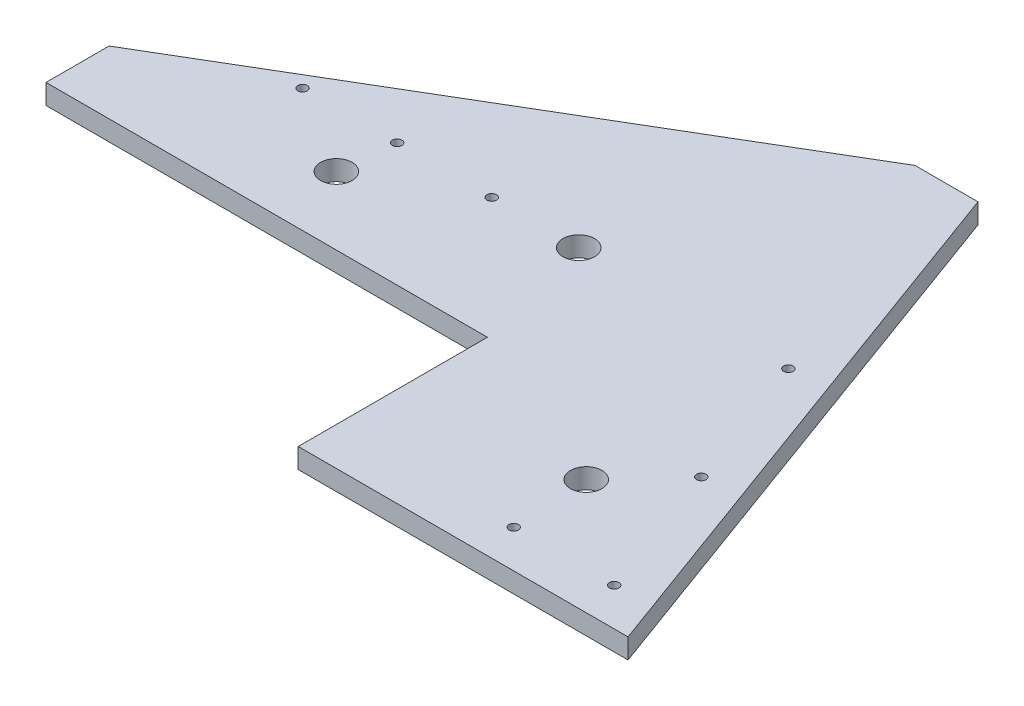
SolidWorks part; units mm, degrees
ref_plane "Front" through (0, 0, 0) normal (0, 0, 1) x (1, 0, 0)
ref_plane "Top" through (0, 0, 0) normal (0, 1, 0) x (1, 0, 0)
ref_plane "Right" through (0, 0, 0) normal (1, 0, 0) x (0, 0, -1)
sketch "Sketch1" plane through (0, 0, 0) normal (0, 1, 0) x (1, 0, 0)
  line L0 (145, 175) -> (180.6, 175)
  line L1 (0, 0) -> (145, 0)
  line L2 (0, 0) -> (0, 175)
  line L3 (0, 175) -> (145, 175)
  line L4 (145, 0) -> (145, 175)
  line L5 (180.6, 175) -> (180.6, 0)
  line L6 (180.6, 0) -> (145, 0)
  line L7 (145, 0) -> (145, 60)
  line L8 (145, 60) -> (140, 60)
  line L9 (140, 60) -> (140, 0)
  line L10 (140, 60) -> (0, 60)
  line L11 (180.6, 175) -> (160.6, 175)
  line L12 (0, 60) -> (0, 80)
  line L13 (160.6, 175) -> (0, 80)
  line L14 (0, 60) -> (70.5, 60)
  line L15 (70.5, 60) -> (70.5, 81.59)
  line L16 (70.5, 81.59) -> (129.875, 81.59)
  line L17 (180.6, 0) -> (244.6, 0)
  line L18 (244.6, 0) -> (180.6, 175)
  line L19 (129.875, 81.59) -> (129.875, 99.09)
  line L20 (244.6, 0) -> (194.75, 0)
  line L21 (194.75, 0) -> (194.75, 36.59)
  circle A0 centre (70.5, 81.59) radius 5
  circle A2 centre (129.875, 99.09) radius 5
  circle A3 centre (194.75, 36.59) radius 5
  dimension "D10" = 59.375
  dimension "D11" = 64
  dimension "D13" = 36.59
  dimension "D1" = 175
  dimension "D2" = 145
  dimension "D3" = 35.6
  dimension "D4" = 60
  dimension "D5" = 5
  dimension "D6" = 20
  dimension "D7" = 20
  dimension "D8" = 70.5
  dimension "D9" = 21.59
  dimension "D12" = 17.5
  dimension "D14" = 49.85
extrude "Boss-Extrude2" add sketch "Sketch1" along normal blind 6.35 contours A2 A0 L10 L8 L4 L13 L2 | L0 L13 L4 L6 L5 | L17 L18 L5 | L8 L9 L1 L4 region at (162.9473, 0, -86.5132) region at (88.7844, 0, -96.4223) region at (202.0355, 0, -58.6426) region at (142.5, 0, -30)
sketch "Sketch3" plane through (0, 6.35, 0) normal (0, 1, 0) x (1, 0, 0)
  line L0 (0, 60) -> (0, 99.0944)
  line L1 (0, 99.0944) -> (42.2796, 99.0944)
  line L2 (42.2796, 99.0944) -> (32.2796, 99.0944)
  line L3 (160.6, 175) -> (0, 80) construction
  line L4 (42.2796, 99.0944) -> (72.2796, 99.0944)
  line L5 (72.2796, 99.0944) -> (102.2796, 99.0944)
  line L6 (102.2796, 99.0944) -> (208.3598, 99.0944)
  line L7 (244.6, 0) -> (180.6, 175) construction
  line L8 (208.3598, 99.0944) -> (196.3598, 99.0944)
  line L9 (244.6, 0) -> (232.0087, 0)
  line L10 (244.6, 0) -> (140, 0) construction
  line L11 (240.2114, 12) -> (228.2114, 12)
  line L12 (228.2114, 12) -> (232.0087, 12)
  line L13 (232.0087, 12) -> (232.0087, 0)
  line L14 (196.3598, 99.0944) -> (228.2114, 12)
  line L15 (228.2114, 12) -> (212.2856, 55.5472)
  line L16 (212.2856, 55.5472) -> (196.3598, 99.0944)
  line L17 (228.2114, 12) -> (196.3598, 12)
  circle A0 centre (42.2796, 99.0944) radius 1.5
  circle A1 centre (72.2796, 99.0944) radius 1.5
  circle A2 centre (102.2796, 99.0944) radius 1.5
  circle A3 centre (196.3598, 99.0944) radius 1.5
  circle A4 centre (212.2856, 55.5472) radius 1.5
  circle A5 centre (228.2114, 12) radius 1.5
  circle A6 centre (196.3598, 12) radius 1.5
  dimension "D5" = 12
  dimension "D6" = 12
  dimension "D1" = 39.0944
  dimension "D2" = 10
  dimension "D3" = 30
  dimension "D4" = 30
  dimension "D7" = 12
extrude "Cut-Extrude1" cut sketch "Sketch3" against normal blind 6.35 contours L2 A0 L4 | L4 A0 L2 | L5 A1 L4 | L4 A1 L5 | A2 | L5 A2 L6 | L6 A3 | L6 A3 | L14 A3 L6 | L14 A4 | L14 A4 | L12 A5 L14 | L14 A5 L17 | L17 A5 L12 | A6 region at (42.2796, 6.35, -99.731) region at (228.7002, 6.35, -12.6992) region at (227.4417, 6.35, -12.5381) region at (212.8835, 6.35, -55.7659) region at (211.6877, 6.35, -55.3285) region at (196.3598, 6.35, -99.731) region at (195.871, 6.35, -98.3952) region at (102.2796, 6.35, -99.731) region at (102.2796, 6.35, -98.4578) region at (72.2796, 6.35, -99.731) region at (72.2796, 6.35, -98.4578) region at (42.2796, 6.35, -98.4578) region at (197.1294, 6.35, -98.5563) region at (228.2114, 6.35, -11.3634)
